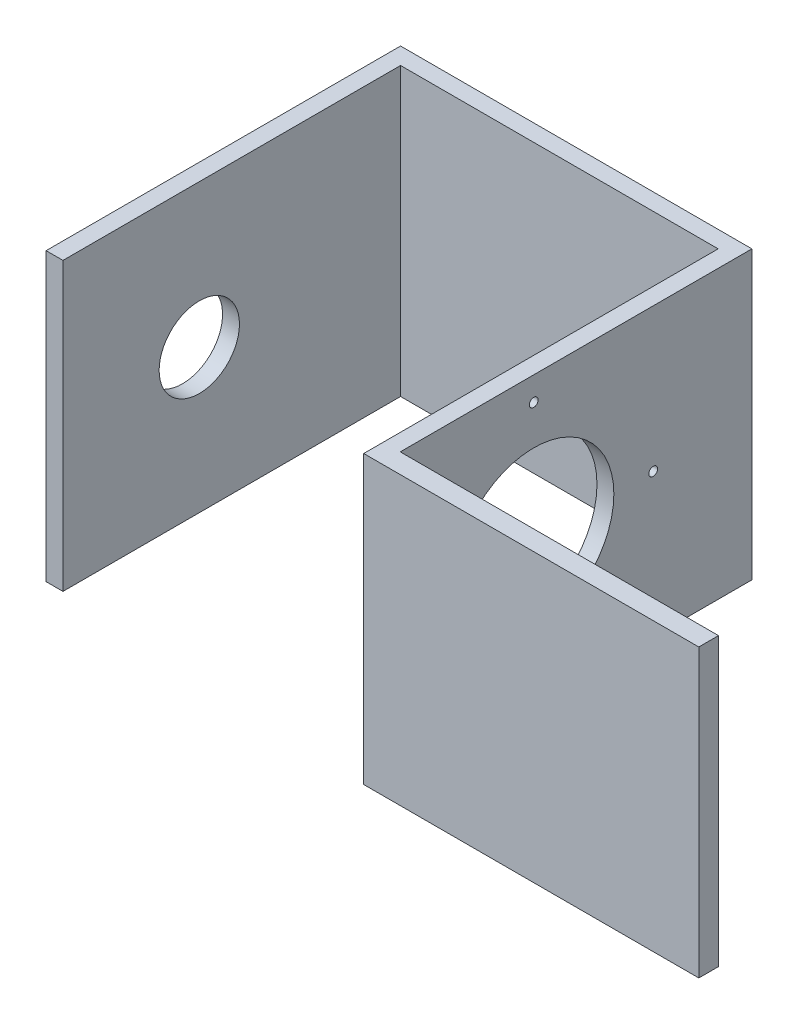
SolidWorks part; units mm, degrees
ref_plane "Front Plane" through (0, 0, 0) normal (0, 0, 1) x (1, 0, 0)
ref_plane "Top Plane" through (0, 0, 0) normal (0, 1, 0) x (1, 0, 0)
ref_plane "Right Plane" through (0, 0, 0) normal (1, 0, 0) x (0, 0, -1)
sketch "Sketch1" plane through (0, 0, 0) normal (0, 1, 0) x (1, 0, 0)
  line L0 (-47.5, -29.9135) -> (47.5, -29.9135) construction
  line L1 (-47.5, 56.6115) -> (47.5, 56.6115) construction
  line L2 (-47.5, 56.6115) -> (-47.5, -56.6115) construction
  line L3 (-47.5, -56.6115) -> (47.5, -56.6115) construction
  line L4 (47.5, 56.6115) -> (47.5, -56.6115) construction
  line L5 (-47.5, 56.6115) -> (47.5, -56.6115) construction
  line L6 (-47.5, -56.6115) -> (47.5, 56.6115) construction
  line L7 (-47.5, -23.9135) -> (47.5, -23.9135) construction
  line L8 (-47.5, 23.5865) -> (47.5, 23.5865) construction
  line L9 (47.5, 27.5865) -> (-47.5, 27.5865) construction
  line L10 (89.198, 47.5) -> (89.198, -47.5) construction
  line L11 (175.723, 47.5) -> (175.723, -47.5) construction
  line L12 (175.723, 47.5) -> (62.5, 47.5) construction
  line L13 (62.5, 47.5) -> (62.5, -47.5) construction
  line L14 (175.723, -47.5) -> (62.5, -47.5) construction
  line L15 (175.723, 47.5) -> (62.5, -47.5) construction
  line L16 (62.5, 47.5) -> (175.723, -47.5) construction
  line L17 (95.198, 47.5) -> (95.198, -47.5) construction
  line L18 (142.698, 47.5) -> (142.698, -47.5) construction
  line L19 (146.698, -47.5) -> (146.698, 47.5) construction
  line L20 (56.5, 71.6115) -> (56.5, -54.5) construction
  line L21 (47.5, -56.6115) -> (-248.4804, -56.6115) construction
  line L22 (47.5, -56.6115) -> (47.5, -62.6115) construction
  line L23 (47.5, -62.6115) -> (-248.4804, -62.6115) construction
  line L24 (-248.4804, -56.6115) -> (-248.4804, -62.6115) construction
  line L25 (56.5, -54.5) -> (319.1082, -54.5) construction
  line L26 (62.5, 77.6115) -> (62.5, -48.5) construction
  line L27 (62.5, -48.5) -> (319.1082, -48.5) construction
  line L28 (62.5, -48.5) -> (62.5, -54.5) construction
  line L29 (62.5, -48.5) -> (56.5, -48.5) construction
  line L30 (47.5, -56.6115) -> (47.5, -62.6115) construction
  line L31 (48.5, 17.5865) -> (48.5, -30) construction
  line L32 (48.5, -30) -> (54.5, -30) construction
  line L33 (54.5, -30) -> (54.5, 23.5865) construction
  line L34 (0, 0) -> (0, 56.6115) construction
  line L35 (-48.5, -30) -> (-54.5, -30) construction
  line L36 (-54.5, -30) -> (-54.5, 23.5865) construction
  line L37 (-48.5, 17.5865) -> (-48.5, -30) construction
  line L38 (54.5, 23.5865) -> (-54.5, 23.5865) construction
  line L39 (-48.5, 17.5865) -> (48.5, 17.5865) construction
  line L40 (48.5, 17.5865) -> (48.5, 23.5865) construction
  line L41 (62.5, 77.6115) -> (-67.952, 77.6115) construction
  line L42 (56.5, 71.6115) -> (-56.5, 71.6115) construction
  line L43 (-56.5, 71.6115) -> (-56.5, -48.5) construction
  line L44 (-56.5, -48.5) -> (-62.5, -48.5) construction
  line L45 (-62.5, -48.5) -> (-62.5, 98.5172) construction
  line L46 (-196.6321, -56.6115) -> (-196.6321, 23.9185) construction
  line L51 (-196.6321, -62.6115) -> (-101.6321, -62.6115) construction
  line L52 (-196.6321, -62.6115) -> (-196.6321, -89.3115) construction
  line L53 (-196.6321, -89.3115) -> (-101.6321, -89.3115) construction
  line L54 (-101.6321, -62.6115) -> (-101.6321, -89.3115) construction
  line L55 (-196.6321, 23.9185) -> (-101.6321, 23.9185) construction
  line L56 (-101.6321, 23.9185) -> (-101.6321, -56.6115) construction
  line L57 (-54.5, -23.9135) -> (-56.5, -23.9135) construction
  line L58 (54.5, -23.9135) -> (56.5, -23.9135) construction
  line L59 (56.5, 71.6115) -> (56.5, 77.6115) construction
  point P0 (0, 0)
  point P17 (119.1115, 0)
  dimension "D1" = 113.223
  dimension "D2" = 95
  dimension "D3" = 6
  dimension "D4" = 26.698
  dimension "D5" = 4
  dimension "D6" = 57.5
  dimension "D7" = 29.025
  dimension "D8" = 6
  dimension "D9" = 95
  dimension "D10" = 6
  dimension "D11" = 26.698
  dimension "D12" = 4
  dimension "D13" = 29.025
  dimension "D14" = 57.5
  dimension "D15" = 30
  dimension "D16" = 1
  dimension "D17" = 1
  dimension "D18" = 2
  dimension "D19" = 26.7
  dimension "D20" = 80.53
  dimension "D21" = 15
sketch "Sketch2" plane through (0, 0, 0) normal (0, 0, 1) x (1, 0, 0)
  line L0 (-47.5, 0) -> (47.5, 0) construction
  line L1 (-47.5, -50) -> (47.5, -50) construction
  line L2 (-47.5, -50) -> (-47.5, 50) construction
  line L3 (-47.5, 50) -> (47.5, 50) construction
  line L4 (47.5, -50) -> (47.5, 50) construction
  line L5 (-47.5, -50) -> (47.5, 50) construction
  line L6 (-47.5, 50) -> (47.5, -50) construction
  line L11 (0, 0) -> (0, 22.5) construction
  line L12 (-196.6321, 0) -> (-101.6321, 0) construction
  line L13 (-196.6321, 0) -> (-101.6321, 0) construction
  line L14 (0, 27.5) -> (-229.1321, 27.5)
  line L15 (-229.1321, 27.5) -> (-229.1321, -27.5)
  line L16 (-229.1321, -27.5) -> (0, -27.5)
  circle A0 centre (0, 0) radius 22.5 construction
  circle A1 centre (0, 22.5) radius 1.5635
  circle A2 centre (22.5, 0) radius 1.5635
  circle A3 centre (0, -22.5) radius 1.5635
  circle A4 centre (-22.5, 0) radius 1.5635
  circle A5 centre (-171.6321, 0) radius 1.5635
  circle A6 centre (-149.1321, 0) radius 22.5 construction
  circle A7 centre (-149.1321, 22.5) radius 1.5635
  circle A8 centre (-126.6321, 0) radius 1.5635
  circle A9 centre (-149.1321, -22.5) radius 1.5635
  arc A10 (0, 27.5) -> (0, -27.5) centre (0, 0) cw
  point P0 (0, 0)
  point P15 (0, 0)
  point P18 (0, 0)
  point P21 (0, 0)
  point P24 (0, 0)
  point P39 (-47.5, 51)
  point P40 (-47.5, -51)
  dimension "D3" = 45
  dimension "D4" = 3.127
  dimension "D7" = 5
  dimension "D1" = 100
  dimension "D2" = 95
  dimension "D8" = 80
  dimension "D9" = 1
  dimension "D6" = 2
  dimension "D5" = 4
extrude "Boss-Extrude1" [suppressed] add sketch "Sketch2" along normal up to vertex from vertex
sketch "Sketch3" plane through (0, 0, 0) normal (0, 1, 0) x (1, 0, 0)
  line L0 (-48.5, -30) -> (-54.5, -30) construction
  line L1 (-48.5, 17.5865) -> (-48.5, -30) construction
  line L2 (-54.5, -30) -> (-54.5, 23.5865) construction
  line L3 (-48.5, 17.5865) -> (48.5, 17.5865) construction
  line L4 (54.5, 23.5865) -> (-54.5, 23.5865) construction
  line L5 (54.5, -30) -> (54.5, 23.5865) construction
  line L6 (48.5, 17.5865) -> (48.5, -30) construction
  line L7 (48.5, -30) -> (54.5, -30) construction
  line L8 (-48.5, -30) -> (-54.5, -30)
  line L9 (-48.5, 17.5865) -> (-48.5, -30)
  line L10 (-54.5, -30) -> (-54.5, 23.5865)
  line L11 (-48.5, 17.5865) -> (48.5, 17.5865)
  line L12 (54.5, 23.5865) -> (-54.5, 23.5865)
  line L13 (54.5, -30) -> (54.5, 23.5865)
  line L14 (48.5, 17.5865) -> (48.5, -30)
  line L15 (48.5, -30) -> (54.5, -30)
extrude "Boss-Extrude2" [suppressed] add sketch "Sketch3" along normal up to vertex and the other way up to vertex
sketch "Sketch4" [suppressed] plane through (0, 0, -17.5865) normal (0, 0, 1) x (1, 0, 0)
  line L1 (30, -45) -> (-30, -45) construction
  line L2 (30, -45) -> (30, 45) construction
  line L3 (30, 45) -> (-30, 45) construction
  line L4 (-30, -45) -> (-30, 45) construction
  line L5 (30, -45) -> (-30, 45) construction
  line L6 (30, 45) -> (-30, -45) construction
  circle A0 centre (0, 0) radius 46.25
  circle A1 centre (-30, 45) radius 2.25
  circle A2 centre (30, 45) radius 2.25
  circle A3 centre (30, -45) radius 2.25
  circle A4 centre (-30, -45) radius 2.25
  dimension "D1" = 92.5
  dimension "D4" = 4.5
  dimension "D2" = 90
  dimension "D3" = 60
extrude "Cut-Extrude1" [suppressed] cut sketch "Sketch4" against normal through all
sketch "Sketch5" [suppressed] plane through (54.5, 0, 0) normal (1, 0, 0) x (0, 0, -1)
  circle A0 centre (0, 0) radius 14.2875
  point P0 (0, 0)
  dimension "D1" = 28.575
extrude "Cut-Extrude2" [suppressed] cut sketch "Sketch5" against normal through all
sketch "Sketch6" plane through (0, 0, 0) normal (0, 1, 0) x (1, 0, 0)
  line L0 (62.5, 77.6115) -> (62.5, -48.5) construction
  line L1 (62.5, 47.5) -> (62.5, -47.5) construction
  line L2 (175.723, -47.5) -> (62.5, -47.5) construction
  line L3 (56.5, -54.5) -> (319.1082, -54.5) construction
  line L4 (56.5, 71.6115) -> (56.5, -54.5) construction
  line L5 (56.5, 71.6115) -> (-56.5, 71.6115) construction
  line L6 (-62.5, -48.5) -> (-62.5, 98.5172) construction
  line L7 (-56.5, -48.5) -> (-62.5, -48.5) construction
  line L8 (-56.5, 71.6115) -> (-56.5, -48.5) construction
  line L9 (62.5, 77.6115) -> (62.5, -47.5)
  line L10 (62.5, 47.5) -> (62.5, -47.5)
  line L11 (175.723, -47.5) -> (62.5, -47.5)
  line L12 (56.5, -54.5) -> (175.723, -54.5)
  line L13 (56.5, 71.6115) -> (56.5, -54.5)
  line L14 (56.5, 71.6115) -> (-56.5, 71.6115)
  line L15 (-62.5, -48.5) -> (-62.5, 77.6115)
  line L16 (-56.5, -48.5) -> (-62.5, -48.5)
  line L17 (-56.5, 71.6115) -> (-56.5, -48.5)
  line L18 (62.5, 77.6115) -> (-62.5, 77.6115)
  line L19 (175.723, -47.5) -> (175.723, -54.5)
extrude "Boss-Extrude3" add sketch "Sketch6" along normal up to vertex (51 mm away) and the other way up to vertex (51 mm away) contours L19 L11 L9 L18 L15 L16 L17 L14 L13 L12 region at (59.776, 0, -62.5558) up to point (-47.5, 51, 0) other way up to point (-47.5, -51, 0)
sketch "Sketch7" plane through (62.5, 0, 0) normal (1, 0, 0) x (0, 0, -1)
  line L0 (47.5, 0) -> (-47.5, 0) construction
  circle A0 centre (0, 0) radius 42.5 construction
  circle A1 centre (0, 42.5) radius 1.5635
  circle A2 centre (42.5, 0) radius 1.5635
  circle A3 centre (0, -42.5) radius 1.5635
  circle A4 centre (-42.5, 0) radius 1.5635
  circle A5 centre (0, 0) radius 28.5
  point P15 (0, 0)
  dimension "D1" = 85
  dimension "D2" = 3.127
  dimension "D4" = 57
  dimension "D3" = 4
extrude "Cut-Extrude3" cut sketch "Sketch7" against normal up to next
sketch "Sketch8" plane through (-62.5, 0, 0) normal (-1, 0, 0) x (0, 0, 1)
  circle A0 centre (0, 0) radius 14.2875
  dimension "D1" = 28.575
extrude "Cut-Extrude4" cut sketch "Sketch8" against normal up to next
